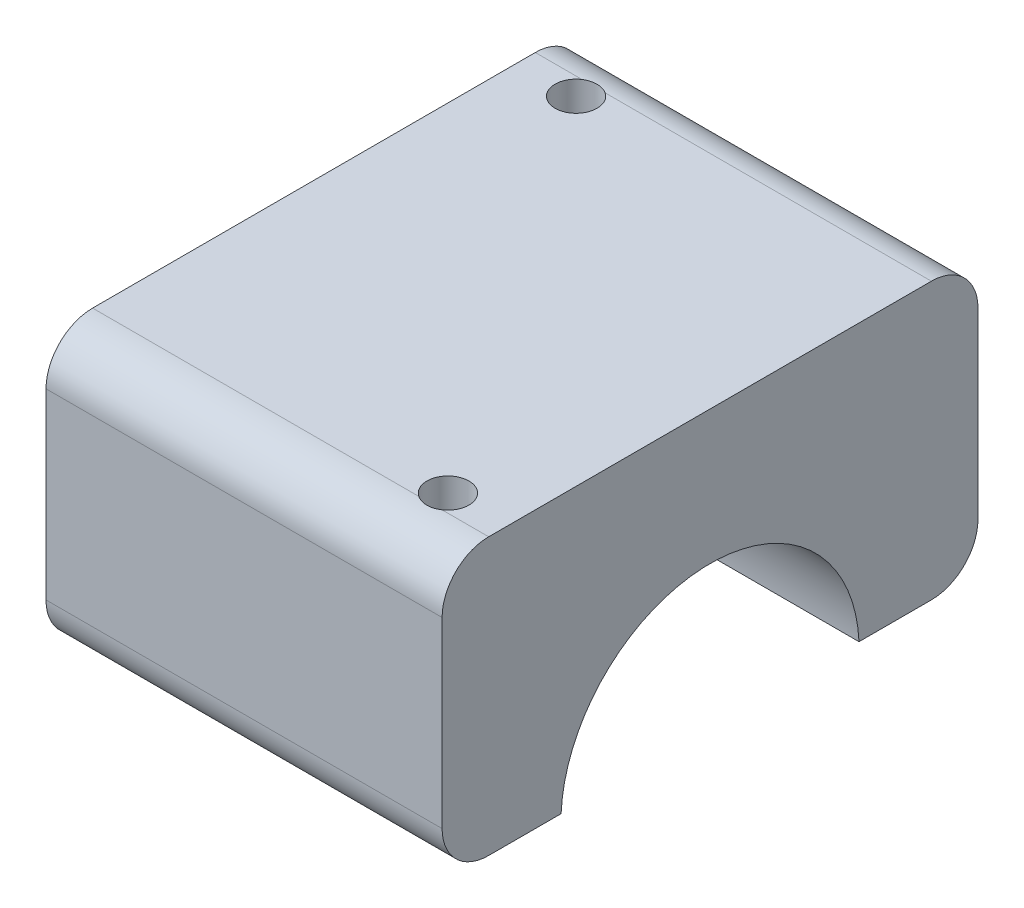
SolidWorks part; units mm, degrees
ref_plane "Front Plane" through (0, 0, 0) normal (0, 0, 1) x (1, 0, 0)
ref_plane "Top Plane" through (0, 0, 0) normal (0, 1, 0) x (1, 0, 0)
ref_plane "Right Plane" through (0, 0, 0) normal (1, 0, 0) x (0, 0, -1)
sketch "Sketch1" plane through (0, 0, 0) normal (1, 0, 0) x (0, 0, -1)
  line L0 (-19, 0.6) -> (19, 0.6)
  line L1 (23, 4.6) -> (23, 20.294)
  line L2 (19, 24.294) -> (-19, 24.294)
  line L3 (-23, 20.294) -> (-23, 4.6)
  arc A0 (19, 0.6) -> (23, 4.6) centre (19, 4.6) ccw
  arc A1 (23, 20.294) -> (19, 24.294) centre (19, 20.294) ccw
  arc A2 (-19, 24.294) -> (-23, 20.294) centre (-19, 20.294) ccw
  arc A3 (-23, 4.6) -> (-19, 0.6) centre (-19, 4.6) ccw
extrude "Boss-Extrude1" add sketch "Sketch1" along normal mid plane 34
sketch "Sketch2" plane through (0, 0, 0) normal (1, 0, 0) x (0, 0, -1)
  circle A0 centre (0, 0) radius 12.8
extrude "Cut-Extrude1" cut sketch "Sketch2" against normal through all and the other way through all
ref_plane "Plane1" through (0, 0.6, 0) normal (0, 1, 0) x (1, 0, 0)
sketch "Sketch3" plane through (0, 0.6, 0) normal (0, 1, 0) x (1, 0, 0)
  circle A0 centre (12, -17.5) radius 1.8
  circle A1 centre (-12, 17.5) radius 1.8
extrude "Cut-Extrude2" cut sketch "Sketch3" along normal blind 24.294
